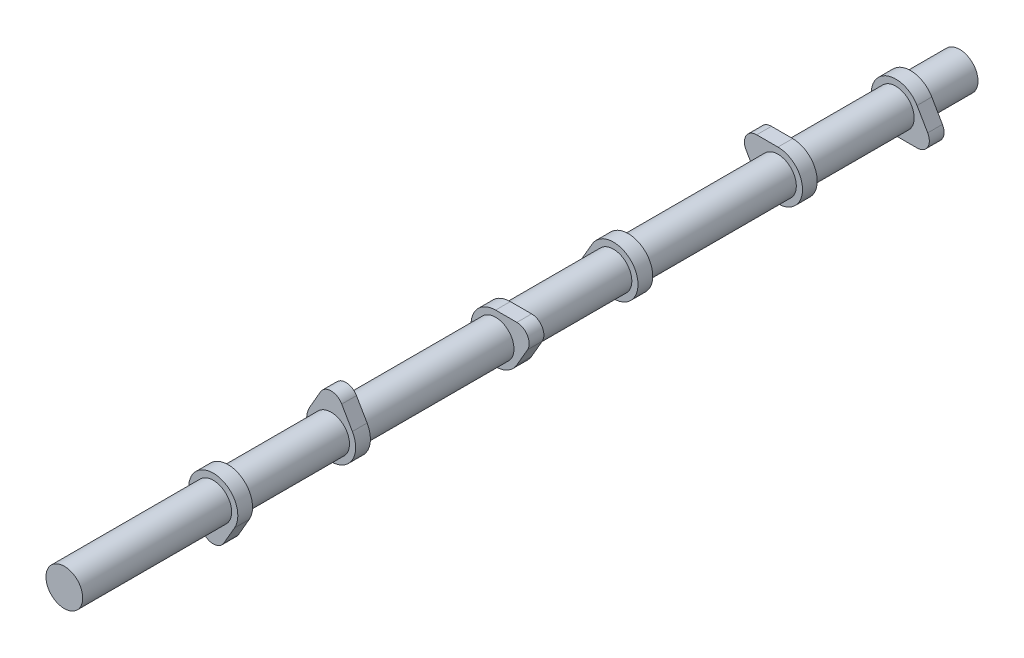
SolidWorks part; units mm, degrees
material "Cast Carbon Steel"
ref_plane "Front Plane" through (0, 0, 0) normal (0, 0, 1) x (1, 0, 0)
ref_plane "Top Plane" through (0, 0, 0) normal (0, 1, 0) x (1, 0, 0)
ref_plane "Right Plane" through (0, 0, 0) normal (1, 0, 0) x (0, 0, -1)
sketch "Schizzo4" plane through (0, 0, 0) normal (0, 0, 1) x (1, 0, 0)
  line L0 (5.4993, 15.875) -> (10.9985, 6.35)
  line L1 (-5.4993, 15.875) -> (-10.9985, 6.35)
  arc A0 (-10.9985, 6.35) -> (10.9985, 6.35) centre (0, 0) ccw
  arc A1 (5.4993, 15.875) -> (-5.4993, 15.875) centre (0, 12.7) ccw
  dimension "D1" = 25.4
  dimension "D2" = 12.7
  dimension "D3" = 12.7
extrude "Estrusione-Estrusione1" add sketch "Schizzo4" along normal blind 7.62
ref_axis "Assi1" through (0, 0, 130.5716) along (0, 0, -1)
move or copy body "Corpo-Sposta/copia7" bodies to move or copy 101 copy yes number of copies 1 translate (0, 0, 60.96) parameters "D1"=0, "D2"=0, "D3"=0
move or copy body "Corpo-Sposta/copia8" bodies to move or copy 110 copy no rotation origin (0, 0, 0) rotation axis (0, 0, 1) rotation angle 180
sketch "Schizzo11" plane through (0, 0, 0) normal (0, 0, 1) x (1, 0, 0)
  circle A0 centre (0, 0) radius 9.5
  dimension "D1" = 19
extrude "Estrusione-Estrusione4" add sketch "Schizzo11" along normal blind 146.05 from offset 25.4 offset against normal yes
pattern_linear "Ripetizione a L1" count 3 spacing 146.05 along (0, 0, -1) of "Estrusione-Estrusione1", "Estrusione-Estrusione4"
move or copy body "Corpo-Sposta/copia9" bodies to move or copy 113 copy no rotation origin (0, 0, 0) rotation axis (0, 0, 1) rotation angle 120
move or copy body "Corpo-Sposta/copia10" bodies to move or copy 114 copy no rotation origin (0, 0, 0) rotation axis (0, 0, -1) rotation angle 120
sketch "Schizzo12" plane through (0, 0, 120.65) normal (0, 0, 1) x (1, 0, 0)
  circle A1 centre (0, 0) radius 9.5
  circle A2 centre (0, 0) radius 9.5
  dimension "D1" = 0
extrude "Estrusione-Estrusione5" add sketch "Schizzo12" along normal blind 24.97
combine bodies "Abbina1" operation type add bodies to combine 116 115 117
